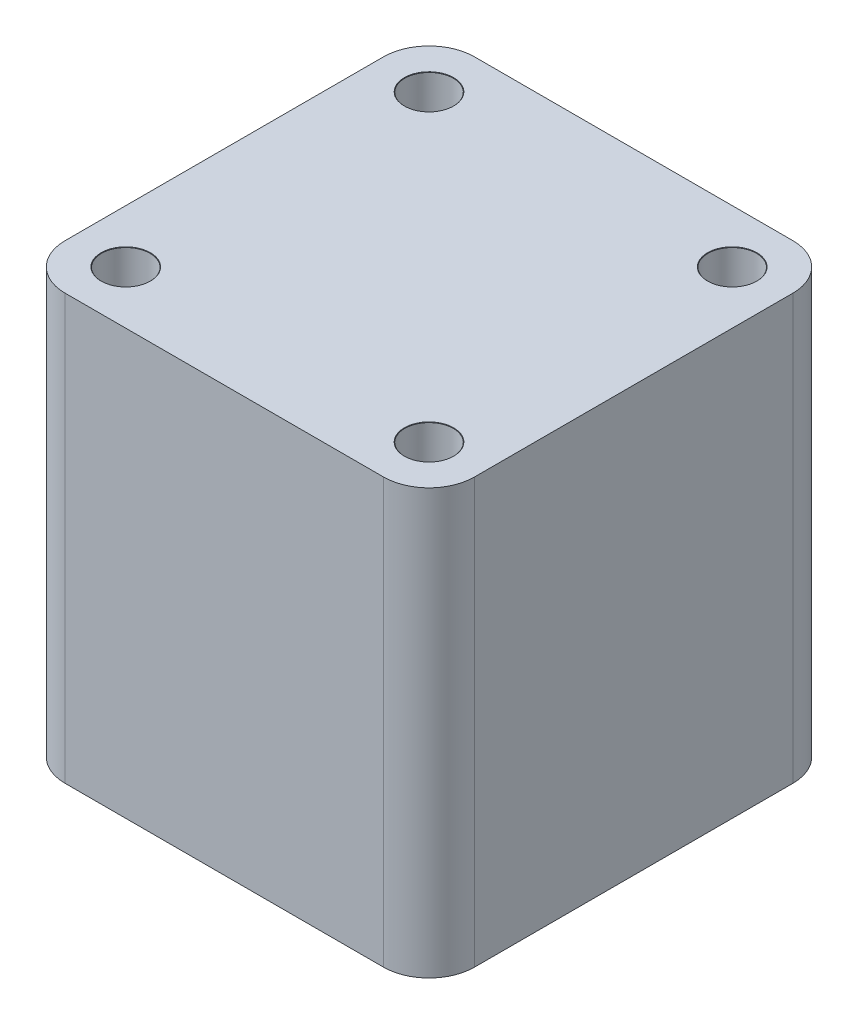
SolidWorks part; units mm, degrees
material "AISI 1045 Steel, cold drawn"
ref_plane "Front Plane" through (0, 0, 0) normal (0, 0, 1) x (1, 0, 0)
ref_plane "Top Plane" through (0, 0, 0) normal (0, 1, 0) x (1, 0, 0)
ref_plane "Right Plane" through (0, 0, 0) normal (1, 0, 0) x (0, 0, -1)
sketch "Sketch1" plane through (0, 0, 0) normal (0, 1, 0) x (1, 0, 0)
  line L1 (13.5, -13.5) -> (-13.5, -13.5)
  line L2 (13.5, -13.5) -> (13.5, 13.5)
  line L3 (13.5, 13.5) -> (-13.5, 13.5)
  line L4 (-13.5, -13.5) -> (-13.5, 13.5)
  line L5 (13.5, -13.5) -> (-13.5, 13.5) construction
  line L6 (13.5, 13.5) -> (-13.5, -13.5) construction
  line L7 (10, -10) -> (-10, -10) construction
  line L8 (10, -10) -> (10, 10) construction
  line L9 (10, 10) -> (-10, 10) construction
  line L10 (-10, -10) -> (-10, 10) construction
  line L11 (10, -10) -> (-10, 10) construction
  line L12 (10, 10) -> (-10, -10) construction
  point P0 (0, 0)
  point P6 (0, 0)
  dimension "D1" = 20
  dimension "D2" = 27
extrude "Boss-Extrude1" add sketch "Sketch1" along normal blind 28
hole_wizard "M3 Clearance Hole1" positions "Sketch2" profile "Sketch4" hole size "M3" standard "ANSI Metric" end condition through all
sketch "Sketch2" plane through (0, 0, 0) normal (0, -1, 0) x (-1, 0, 0)
  point P0 (-10, 10)
  point P3 (10, 10)
  point P6 (10, -10)
  point P9 (-10, -10)
sketch "Sketch4" plane through (10, 0, -10) normal (1, 0, 0) x (0, 0, -1)
  line L0 (0, 0) -> (0, 28)
  line L1 (0, 28) -> (1.625, 28)
  line L2 (1.6, 27.975) -> (1.6, 0.025)
  line L3 (1.6, 0.025) -> (1.625, 0)
  line L5 (1.625, 0) -> (0, 0)
  line L6 (-1.6, 0.025) -> (-1.625, 0) construction
  line L7 (1.625, 28) -> (1.6, 27.975)
  line L8 (-1.625, 28) -> (-1.6, 27.975) construction
  line L11 (0, -6.35) -> (0, 107.95) construction
  dimension "Thru Hole Dia." = 3.2
  dimension "Thru Hole Depth" = 28
  dimension "Near C'Sink Dia." = 3.25
  dimension "Near C'Sink Angle" = 90
  dimension "Far C'Sink Dia." = 3.25
  dimension "Far C'Sink Angle" = 90
fillet "Fillet1" radius 3 4 edges at (13.5, 14, 13.5) (-13.5, 14, 13.5) (13.5, 14, -13.5) (-13.5, 14, -13.5)
